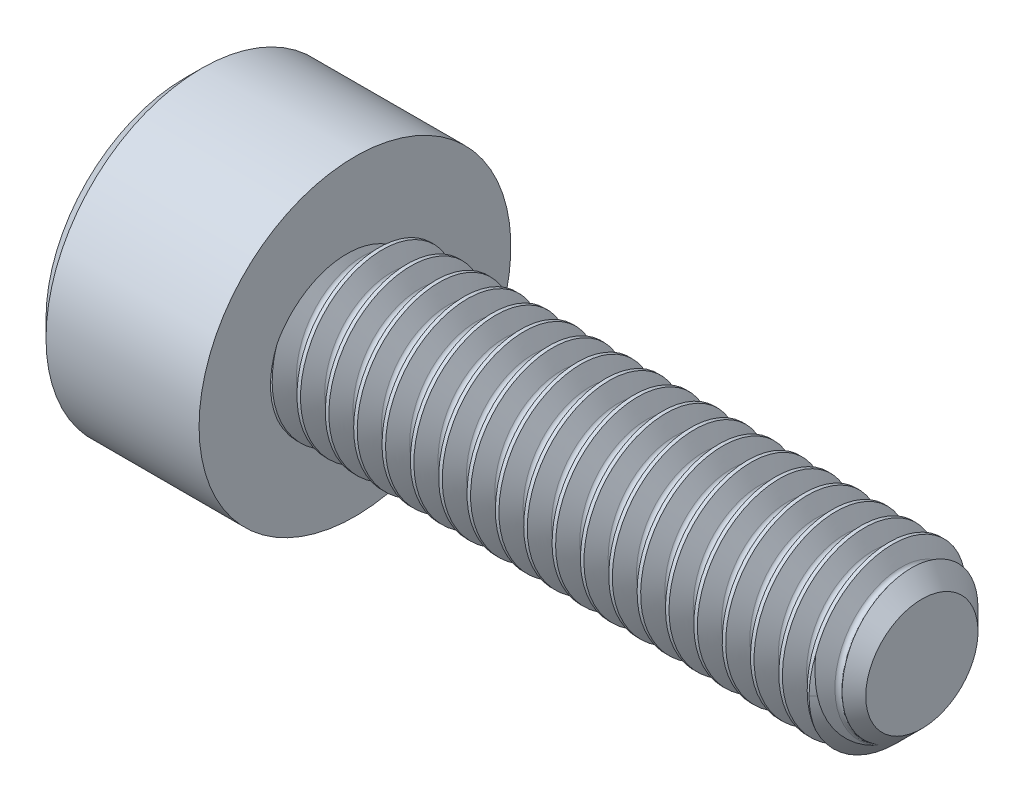
SolidWorks part; units mm, degrees
material "AISI Type 316L stainless steel"
ref_plane "Front Plane" through (0, 0, 0) normal (0, 0, 1) x (1, 0, 0)
ref_plane "Top Plane" through (0, 0, 0) normal (0, 1, 0) x (1, 0, 0)
ref_plane "Right Plane" through (0, 0, 0) normal (1, 0, 0) x (0, 0, -1)
sketch "Sketch1" plane through (0, 0, 0) normal (0, 0, 1) x (1, 0, 0)
  line L0 (-88.7055, 0) -> (96.9812, 0) construction
  line L1 (0, 0) -> (0, 2.75)
  line L2 (0, 2.75) -> (3, 2.75)
  line L4 (13, 0) -> (13, 1.49)
  line L5 (13, 1.49) -> (3, 1.49)
  line L6 (3, 1.49) -> (3, 2.75)
  line L7 (0, 0) -> (13, 0)
revolve "Revolve1" add sketch "Sketch1" angle 360 about L0
chamfer "Chamfer1" distance 0.5 angle 45 1 edges at (13, 0, 1.49)
chamfer "Chamfer2" distance 0.3 angle 45 1 edges at (0, 0, 2.75)
sketch "Sketch3" plane through (0, 0, 0) normal (1, 0, 0) x (0, 0, -1)
  line L1 (-1.4434, 0) -> (-0.7217, -1.25)
  line L2 (-0.7217, -1.25) -> (0.7217, -1.25)
  line L3 (0.7217, -1.25) -> (1.4434, 0)
  line L4 (1.4434, 0) -> (0.7217, 1.25)
  line L5 (0.7217, 1.25) -> (-0.7217, 1.25)
  line L6 (-0.7217, 1.25) -> (-1.4434, 0)
  circle A0 centre (0, 0) radius 1.25 construction
extrude "Cut-Extrude1" cut sketch "Sketch3" along normal blind 2.5
chamfer "Chamfer3" distance 0.3 angle 45 6 edges at (0, 1.25, 0) (0, 0.625, 1.0825) (0, -0.625, 1.0825) (0, -1.25, 0) (0, -0.625, -1.0825) (0, 0.625, -1.0825)
sketch "Sketch5" plane through (13, 0, 0) normal (1, 0, 0) x (0, 0, -1)
  circle A0 centre (0, 0) radius 1.49
curve "Helix/Spiral1" pitch 0.5 height 10 turns 20
sketch "Sketch8" plane through (0, 0, 0) normal (0, 1, 0) x (1, 0, 0)
  line L0 (13, 1.49) -> (13, 1.1111) construction
  line L1 (13.0625, 1.2194) -> (13.3281, 1.6794)
  line L2 (13.3281, 1.6794) -> (12.6719, 1.6794)
  line L3 (12.6719, 1.6794) -> (12.9375, 1.2194)
  line L4 (13, -0.99) -> (13, 0.99) construction
  circle A0 centre (13, 1.49) radius 0.1894 construction
  arc A1 (13.0625, 1.2194) -> (12.9375, 1.2194) centre (13, 1.2555) cw
  dimension "D2" = 0.0722
  dimension "D1" = 0.3789
sweep "Cut-Sweep1" cut profiles "Sketch8" path "Helix/Spiral1" align with end faces yes
